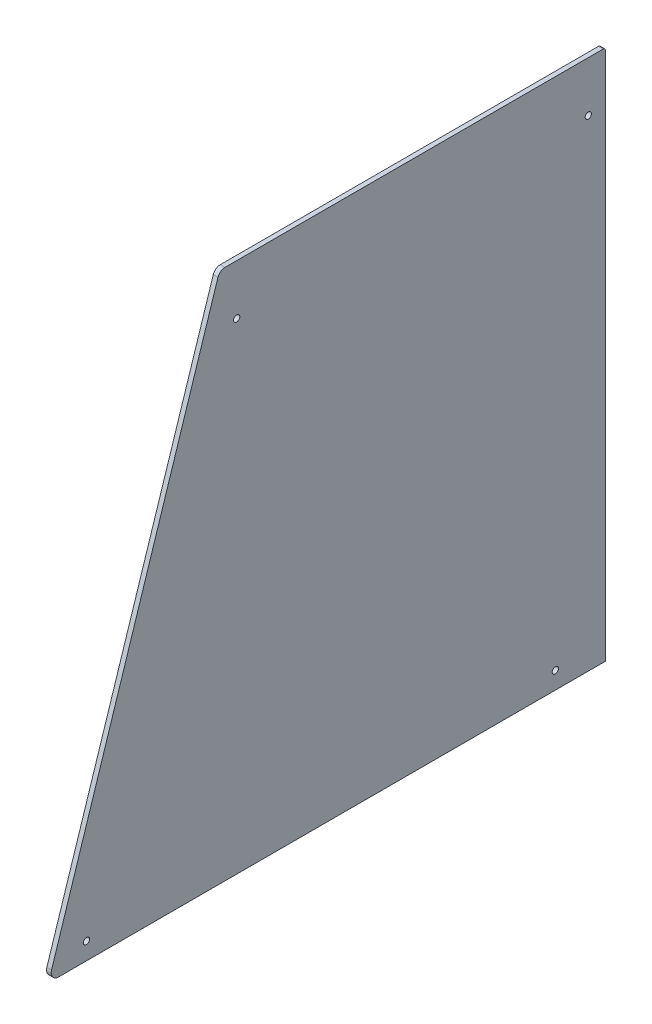
SolidWorks part; units mm, degrees
ref_plane "Front Plane" through (0, 0, 0) normal (0, 0, 1) x (1, 0, 0)
ref_plane "Top Plane" through (0, 0, 0) normal (0, 1, 0) x (1, 0, 0)
ref_plane "Right Plane" through (0, 0, 0) normal (1, 0, 0) x (0, 0, -1)
sketch "Sketch1" plane through (110.5, 0, 0) normal (1, 0, 0) x (0, 0, -1)
  line L0 (122.5, 328.5) -> (122.5, -10)
  line L1 (122.5, 310) -> (122.5, 328.5) construction
  line L2 (122.5, -10) -> (-227.5, -10)
  line L3 (-231.9672, -3.8678) -> (-125.4686, 326.7458)
  line L4 (-121.0014, 330) -> (121, 330)
  arc A0 (-227.5, -10) -> (-231.9672, -3.8678) centre (-227.5, -5.3068) cw
  arc A1 (-125.4686, 326.7458) -> (-121.0014, 330) centre (-121.0014, 325.3068) cw
  arc A2 (-121.0014, 330) -> (-125.4686, 326.7458) centre (-121.0014, 325.3068) ccw construction
  arc A3 (121, 330) -> (122.5, 328.5) centre (121, 328.5) cw
  point P20 (-121.0014, 330)
extrude "Boss-Extrude1" add sketch "Sketch1" against normal blind 3
sketch "Sketch2" plane through (110.5, 0, 0) normal (1, 0, 0) x (0, 0, -1)
  circle A0 centre (111.5014, 297.911) radius 2
  circle A1 centre (90.411, 0.9986) radius 2
  circle A2 centre (-209.589, 0.9986) radius 2
  circle A3 centre (-113.4986, 297.911) radius 2
  point P8 (-113.4986, 297.911)
  point P10 (111.5014, 297.911)
  point P12 (90.411, 0.9986)
  point P14 (0, 0)
  dimension "D1" = 4
  dimension "D2" = 300
extrude "Cut-Extrude2" cut sketch "Sketch2" against normal up to next
